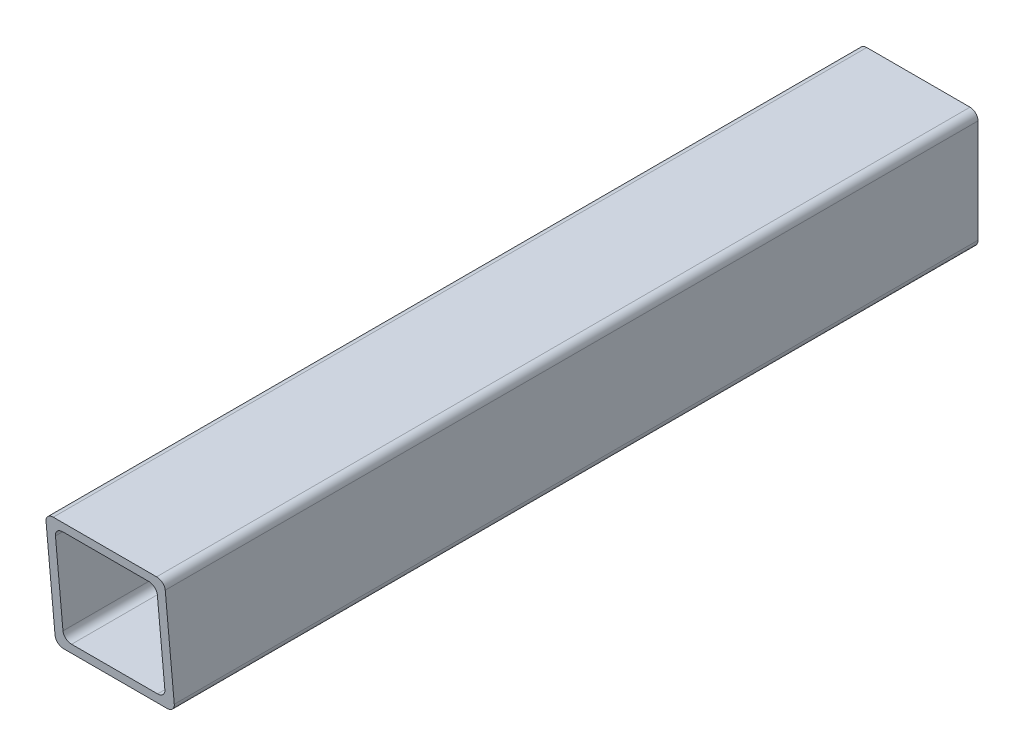
SolidWorks part; units mm, degrees
material "ASTM A500 Grade B Steel"
ref_plane "Front Plane" through (0, 0, 0) normal (0, 0, 1) x (1, 0, 0)
ref_plane "Top Plane" through (0, 0, 0) normal (0, 1, 0) x (1, 0, 0)
ref_plane "Right Plane" through (0, 0, 0) normal (1, 0, 0) x (0, 0, -1)
sketch "Sketch1" plane through (0, 0, 0) normal (0, 0, 1) x (1, 0, 0)
  line L0 (5.3086, -2.7686) -> (32.7914, -2.7686)
  line L1 (2.54, 0) -> (35.56, 0)
  line L2 (0, -2.54) -> (0, -35.56)
  line L3 (2.54, -38.1) -> (35.56, -38.1)
  line L4 (38.1, -2.54) -> (38.1, -35.56)
  line L5 (35.3314, -5.3086) -> (35.3314, -32.7914)
  line L6 (5.3086, -35.3314) -> (32.7914, -35.3314)
  line L7 (2.7686, -5.3086) -> (2.7686, -32.7914)
  line L8 (0, 0) -> (0, -38.1) construction
  line L9 (0, -38.1) -> (38.1, -38.1) construction
  line L10 (38.1, 0) -> (38.1, -38.1) construction
  line L11 (2.7686, -2.7686) -> (2.7686, -35.3314) construction
  line L12 (2.7686, -35.3314) -> (35.3314, -35.3314) construction
  line L13 (35.3314, -2.7686) -> (35.3314, -35.3314) construction
  line L14 (2.7686, -2.7686) -> (35.3314, -2.7686) construction
  line L15 (0, 0) -> (38.1, 0) construction
  arc A0 (0, -35.56) -> (2.54, -38.1) centre (2.54, -35.56) ccw
  arc A1 (38.1, -35.56) -> (35.56, -38.1) centre (35.56, -35.56) cw
  arc A2 (2.7686, -32.7914) -> (5.3086, -35.3314) centre (5.3086, -32.7914) ccw
  arc A3 (32.7914, -35.3314) -> (35.3314, -32.7914) centre (32.7914, -32.7914) ccw
  arc A4 (35.3314, -5.3086) -> (32.7914, -2.7686) centre (32.7914, -5.3086) ccw
  arc A5 (38.1, -2.54) -> (35.56, 0) centre (35.56, -2.54) ccw
  arc A6 (0, -2.54) -> (2.54, 0) centre (2.54, -2.54) cw
  arc A7 (5.3086, -2.7686) -> (2.7686, -5.3086) centre (5.3086, -5.3086) ccw
  point P12 (0, -38.1)
  dimension "D4" = 2.54
  dimension "D3" = 2.7686
extrude "Boss-Extrude1" add sketch "Sketch1" along normal blind 260
sketch "Sketch2" plane through (38.1, 0, 0) normal (1, 0, 0) x (0, 0, -1)
  line L0 (-260, 0) -> (-256.6667, -38.1)
  line L1 (-260, -38.1) -> (0, -38.1) construction
  line L5 (-260, 0) -> (-260, -38.1)
  line L6 (-256.6667, -38.1) -> (-260, -38.1)
  dimension "D1" = 5
extrude "Cut-Extrude1" cut sketch "Sketch2" against normal through all
